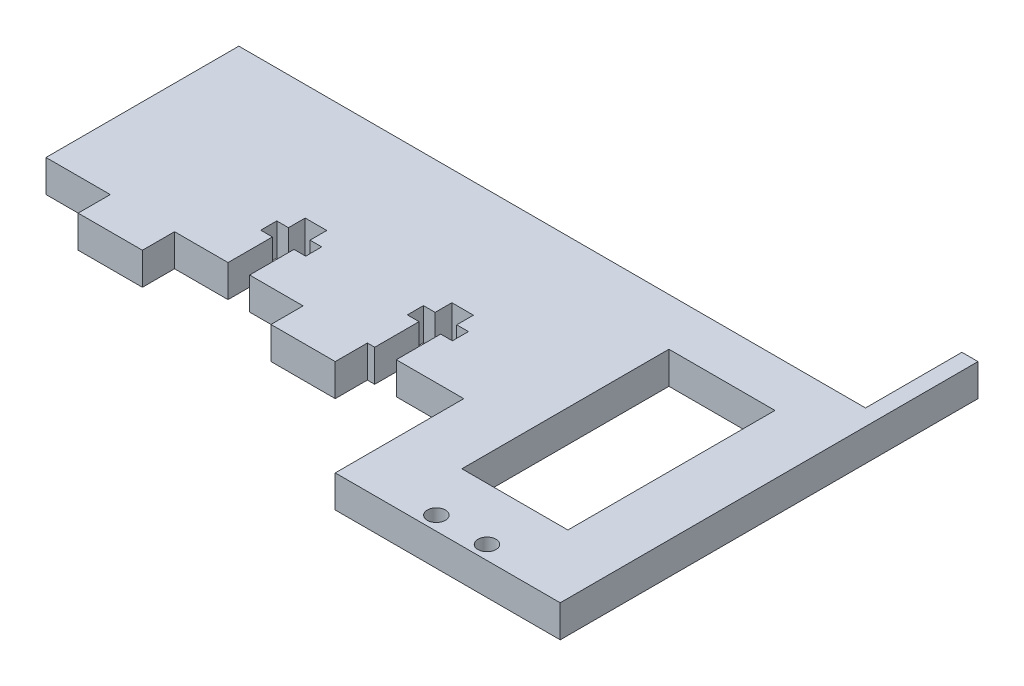
SolidWorks part; units mm, degrees
ref_plane "Front Plane" through (0, 0, 0) normal (0, 0, 1) x (1, 0, 0)
ref_plane "Top Plane" through (0, 0, 0) normal (0, 1, 0) x (1, 0, 0)
ref_plane "Right Plane" through (0, 0, 0) normal (1, 0, 0) x (0, 0, -1)
sketch "Sketch1" plane through (0, 0, 0) normal (0, 1, 0) x (1, 0, 0)
  line L0 (64.8104, 44.2474) -> (64.8104, -38.3026)
  line L1 (-62.1896, 44.2474) -> (64.8104, 44.2474)
  line L2 (-62.1896, 44.2474) -> (-62.1896, -12.9026)
  line L3 (-62.1896, -12.9026) -> (-49.4896, -12.9026)
  line L4 (-36.7896, -12.9026) -> (-11.3896, -12.9026)
  line L6 (1.3104, -12.9026) -> (1.3104, -19.2526)
  line L7 (64.8104, -38.3026) -> (20.3604, -38.3026)
  line L8 (20.3604, -12.9026) -> (20.3604, -38.3026)
  line L9 (1.3104, -19.2526) -> (-11.3896, -19.2526)
  line L10 (-11.3896, -12.9026) -> (-11.3896, -19.2526)
  line L11 (1.3104, -12.9026) -> (20.3604, -12.9026)
  line L12 (-36.7896, -12.9026) -> (-36.7896, -19.2526)
  line L13 (-36.7896, -19.2526) -> (-49.4896, -19.2526)
  line L14 (-49.4896, -12.9026) -> (-49.4896, -19.2526)
  dimension "D1" = 25.4
  dimension "D2" = 57.15
  dimension "D3" = 6.35
  dimension "D4" = 6.35
  dimension "D5" = 12.7
  dimension "D6" = 12.7
  dimension "D7" = 25.4
  dimension "D8" = 19.05
  dimension "D9" = 44.45
  dimension "D10" = 12.7
extrude "Boss-Extrude1" add sketch "Sketch1" along normal blind 6.35
sketch "Sketch2" plane through (0, 0, 0) normal (0, -1, 0) x (1, 0, 0)
  line L0 (20.3604, 12.9026) -> (23.5354, 21.6555)
  line L1 (61.6354, 21.6555) -> (61.6354, -44.2474)
  line L2 (64.8104, -44.2474) -> (-62.1896, -44.2474) construction
  line L3 (61.6354, -44.2474) -> (64.8104, -44.2474)
  line L4 (64.8104, -44.2474) -> (64.8104, 38.3026)
  line L5 (64.8104, 38.3026) -> (64.8104, -44.2474) construction
  line L6 (64.8104, 38.3026) -> (20.3604, 38.3026)
  line L7 (20.3604, 38.3026) -> (20.3604, 12.9026)
  arc A0 (61.6354, 21.6555) -> (23.5354, 21.6555) centre (42.5854, 21.6555) ccw
extrude "Cut-Extrude1" cut sketch "Sketch2" against normal through all rebuild error yes
sketch "Sketch4" plane through (0, 0, 0) normal (0, -1, 0) x (1, 0, 0)
  line L1 (32.1671, 25.0919) -> (53.1176, 25.0919)
  line L2 (32.1671, 25.0919) -> (32.1671, -15.8271)
  line L3 (32.1671, -15.8271) -> (53.1176, -15.8271)
  line L4 (53.1176, 25.0919) -> (53.1176, -15.8271)
extrude "Cut-Extrude2" cut sketch "Sketch4" against normal through all
sketch "Sketch5" plane through (0, 6.35, 0) normal (0, 1, 0) x (1, 0, 0)
  line L0 (-62.1896, 44.2474) -> (-62.1896, -12.9026) construction
  line L1 (61.6354, 44.2474) -> (-62.1896, 44.2474)
  line L2 (61.6354, 44.2474) -> (61.6354, 25.1974)
  line L3 (61.6354, 25.1974) -> (-62.1896, 25.1974)
  line L4 (-62.1896, 44.2474) -> (-62.1896, 25.1974)
  circle A0 centre (47.5854, -35.551) radius 1.778
  circle A1 centre (37.5854, -35.551) radius 1.778
  circle A2 centre (47.5854, 13.449) radius 1.778
  circle A3 centre (37.5854, 13.449) radius 1.778
  dimension "D1" = 19.05
extrude "Cut-Extrude3" cut sketch "Sketch5" against normal through all
sketch "Sketch6" plane through (0, 6.35, 0) normal (0, 1, 0) x (1, 0, 0)
  line L1 (-36.7896, -12.9026) -> (-11.3896, -12.9026) construction
  line L2 (-24.0896, -12.9026) -> (-24.0896, 2.4668) construction
  line B0 (2.759, -12.9026) -> (7.0262, -12.9026)
  line B1 (7.0262, -0.9646) -> (9.3376, -0.9646)
  line B2 (9.3376, -0.9646) -> (9.3376, -4.1396)
  line B3 (9.3376, -4.1396) -> (7.0262, -4.1396)
  line B4 (7.0262, -4.1396) -> (7.0262, -12.9026)
  line B5 (7.0262, -0.9646) -> (7.0262, 2.3374)
  line B6 (7.0262, 2.3374) -> (2.759, 2.3374)
  line B7 (2.759, -0.9646) -> (2.759, 2.3374)
  line B8 (2.759, -4.1396) -> (2.759, -12.9026)
  line B9 (0.4476, -4.1396) -> (2.759, -4.1396)
  line B10 (0.4476, -0.9646) -> (0.4476, -4.1396)
  line B11 (2.759, -0.9646) -> (0.4476, -0.9646)
  line B12 (-26.2232, -12.9026) -> (-21.956, -12.9026)
  line B13 (-21.956, -0.9646) -> (-19.6446, -0.9646)
  line B14 (-19.6446, -0.9646) -> (-19.6446, -4.1396)
  line B15 (-19.6446, -4.1396) -> (-21.956, -4.1396)
  line B16 (-21.956, -4.1396) -> (-21.956, -12.9026)
  line B17 (-21.956, -0.9646) -> (-21.956, 2.3374)
  line B18 (-21.956, 2.3374) -> (-26.2232, 2.3374)
  line B19 (-26.2232, -0.9646) -> (-26.2232, 2.3374)
  line B20 (-26.2232, -4.1396) -> (-26.2232, -12.9026)
  line B21 (-28.5346, -4.1396) -> (-26.2232, -4.1396)
  line B22 (-28.5346, -0.9646) -> (-28.5346, -4.1396)
  line B23 (-26.2232, -0.9646) -> (-28.5346, -0.9646)
sketch_block_instance "TSlot-1"
sketch_block "TSlot" parameters "D1"=3.302, "D2"=3.175
sketch_block_instance "TSlot-3"
extrude "Cut-Extrude4" cut sketch "Sketch6" against normal through all
